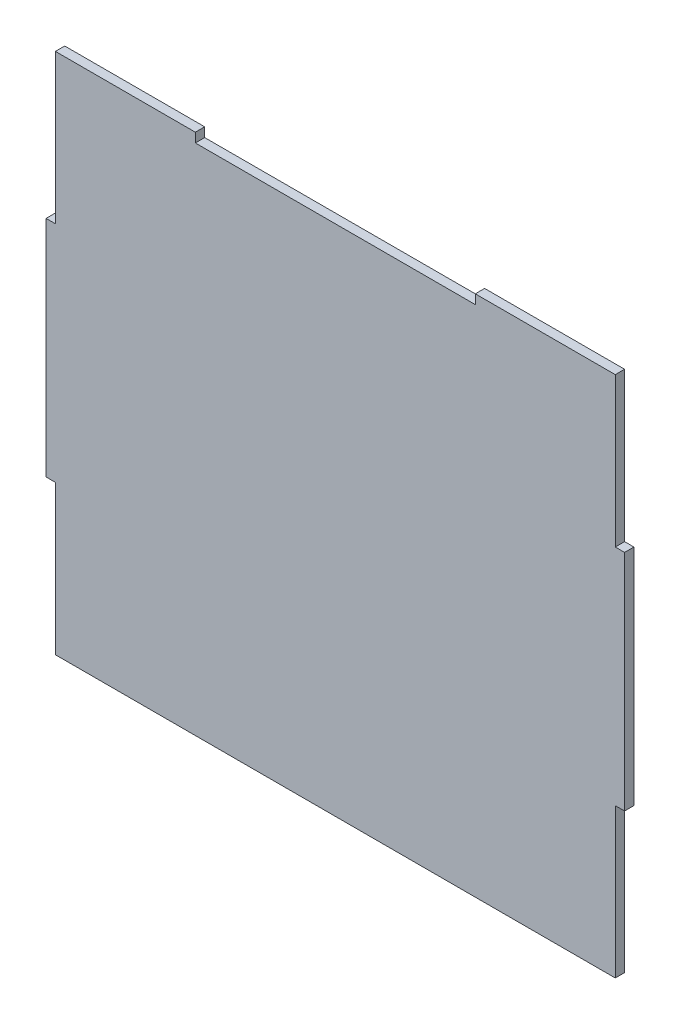
SolidWorks part; units mm, degrees
ref_plane "Ebene vorne" through (0, 0, 0) normal (0, 0, 1) x (1, 0, 0)
ref_plane "Ebene oben" through (0, 0, 0) normal (0, 1, 0) x (1, 0, 0)
ref_plane "Ebene rechts" through (0, 0, 0) normal (1, 0, 0) x (0, 0, -1)
sketch "Skizze1" plane through (0, 0, 0) normal (0, 0, 1) x (1, 0, 0)
  line L1 (-155, 140) -> (155, 140)
  line L2 (-155, 140) -> (-155, -140)
  line L3 (-155, -140) -> (155, -140)
  line L4 (155, 140) -> (155, -140)
  line L5 (-155, 140) -> (155, -140) construction
  line L6 (-155, -140) -> (155, 140) construction
  point P0 (0, 0)
  dimension "D1" = 280
  dimension "D2" = 310
extrude "Aufsatz-Linear austragen1" add sketch "Skizze1" along normal blind 5
sketch "Skizze2" plane through (0, 0, 5) normal (0, 0, 1) x (1, 0, 0)
  line L0 (0, 140) -> (0, -140) construction
  line L1 (155, 140) -> (-155, 140) construction
  line L2 (-155, -140) -> (155, -140) construction
  line L3 (155, -60) -> (150, -60)
  line L4 (-155, 140) -> (-150, 140)
  line L5 (-155, 140) -> (-155, 60)
  line L6 (-155, 60) -> (-150, 60)
  line L7 (-150, 140) -> (-150, 60)
  line L8 (-155, -140) -> (-150, -140)
  line L9 (-155, -140) -> (-155, -60)
  line L10 (-155, -60) -> (-150, -60)
  line L11 (-150, -140) -> (-150, -60)
  line L12 (155, -140) -> (155, -60)
  line L13 (155, -140) -> (150, -140)
  line L14 (155, 60) -> (150, 60)
  line L15 (155, 140) -> (155, 60)
  line L16 (155, 140) -> (150, 140)
  line L17 (150, -140) -> (150, -60)
  line L18 (150, 140) -> (150, 60)
  dimension "D1" = 5
  dimension "D2" = 80
extrude "Schnitt-Linear austragen1" cut sketch "Skizze2" against normal up to surface (5 mm away) up to face at (0, 0, 0)
sketch "Skizze3" plane through (0, 0, 5) normal (0, 0, 1) x (1, 0, 0)
  line L0 (0, 140) -> (0, -140) construction
  line L1 (150, 140) -> (-150, 140) construction
  line L2 (-150, -140) -> (150, -140) construction
  line L7 (75, 140) -> (-75, 140)
  line L8 (-75, 140) -> (-75, 135)
  line L9 (-75, 135) -> (75, 135)
  line L10 (75, 140) -> (75, 135)
  point P10 (0, 135)
  dimension "D1" = 150
  dimension "D2" = 5
extrude "Schnitt-Linear austragen2" cut sketch "Skizze3" against normal through all
